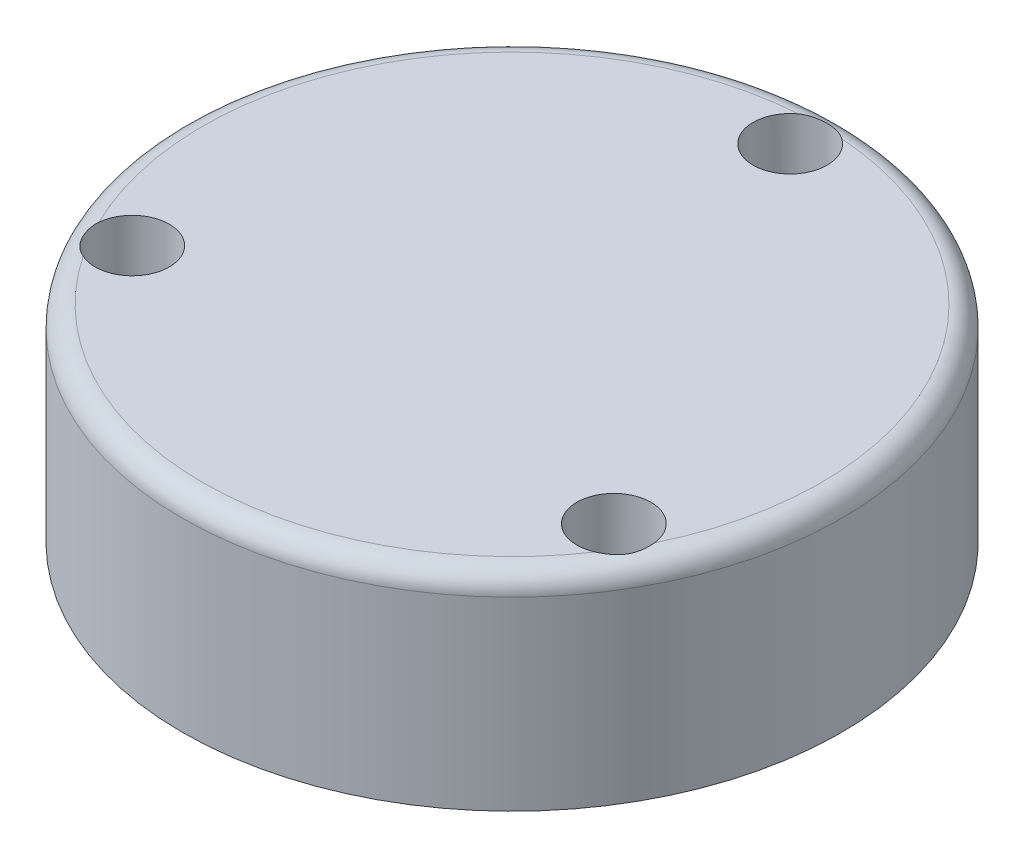
SolidWorks part; units mm, degrees
ref_plane "Спереди" through (0, 0, 0) normal (0, 0, 1) x (1, 0, 0)
ref_plane "Сверху" through (0, 0, 0) normal (0, 1, 0) x (1, 0, 0)
ref_plane "Справа" through (0, 0, 0) normal (1, 0, 0) x (0, 0, -1)
sketch "Эскиз1" plane through (0, 0, 0) normal (0, 1, 0) x (1, 0, 0)
  circle A0 centre (0, 0) radius 16
  dimension "D1" = 32
extrude "Бобышка-Вытянуть1" add sketch "Эскиз1" along normal blind 10
sketch "Эскиз3" plane through (0, 0, 0) normal (0, -1, 0) x (-1, 0, 0)
  line L0 (0, 60.1908) -> (0, -20) construction
  line L1 (0, -20) -> (69.2842, -20) construction
  line L5 (-9, -70) -> (9, -70)
  line L6 (-9, -70) -> (-9, 30)
  line L7 (-9, 30) -> (9, 30)
  line L8 (9, -70) -> (9, 30)
  line L9 (0, 30) -> (0, -70) construction
  line L10 (-9, -20) -> (9, -20) construction
  dimension "D2" = 100
  dimension "D1" = 18
  dimension "D3" = 20
extrude "Бобышка-Вытянуть2" [suppressed] add sketch "Эскиз3" along normal blind 12
sketch "Эскиз2" plane through (0, 10, 0) normal (0, 1, 0) x (1, 0, 0)
  line L0 (0, 18.4133) -> (0, 0) construction
  line L1 (0, 0) -> (22.5214, 0) construction
  circle A0 centre (0, 0) radius 13.5 construction
  circle A1 centre (0, 13.5) radius 1.8
  circle A2 centre (11.6913, -6.75) radius 1.8
  circle A3 centre (-11.6913, -6.75) radius 1.8
  dimension "D1" = 27
  dimension "D2" = 3.6
  dimension "D3" = 3
extrude "Вырез-Вытянуть1" cut sketch "Эскиз2" against normal blind 20
fillet "Скругление1" radius 1 1 edges at (0, 10, 16)
sketch "Эскиз4" [suppressed] plane through (0, 0, -30) normal (0, 0, -1) x (-1, 0, 0)
  line L0 (0, -1.5497) -> (0, -9) construction
  line L1 (0, -9) -> (15.3096, -9) construction
  line L2 (9, -12) -> (-9, -12) construction
  circle A0 centre (0, -9) radius 8
  dimension "D1" = 3
extrude "Вырез-Вытянуть2" [suppressed] cut sketch "Эскиз4" against normal through all
fillet "Скругление2" radius 0.5 3 edges at (11.6913, 0, 8.55) (-11.6913, 0, 8.55) (0, 0, -11.7)
